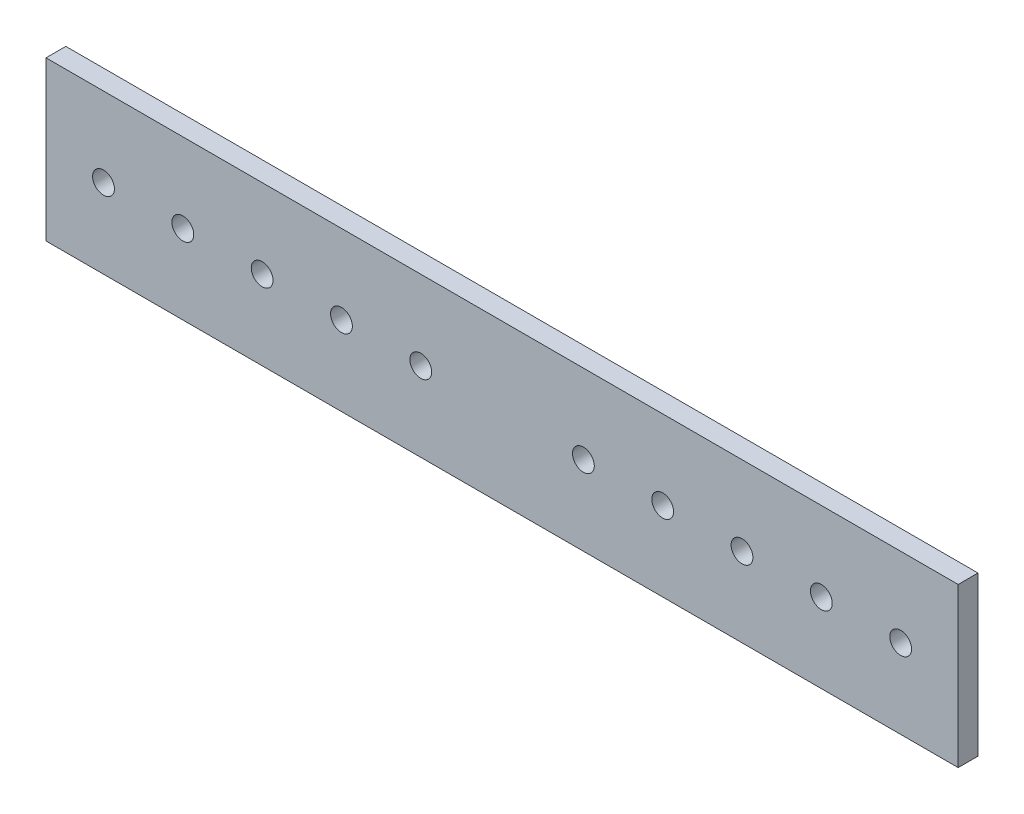
SolidWorks part; units mm, degrees
ref_plane "Plan de face" through (0, 0, 0) normal (0, 0, 1) x (1, 0, 0)
ref_plane "Plan de dessus" through (0, 0, 0) normal (0, 1, 0) x (1, 0, 0)
ref_plane "Plan de droite" through (0, 0, 0) normal (1, 0, 0) x (0, 0, -1)
sketch "Esquisse1" plane through (0, 0, 0) normal (0, 0, 1) x (1, 0, 0)
  line L1 (-115, -20) -> (115, -20)
  line L2 (-115, -20) -> (-115, 20)
  line L3 (-115, 20) -> (115, 20)
  line L4 (115, -20) -> (115, 20)
  line L5 (-115, -20) -> (115, 20) construction
  line L6 (-115, 20) -> (115, -20) construction
  point P0 (0, 0)
  dimension "D1" = 230
  dimension "D2" = 40
extrude "Boss.-Extru.1" add sketch "Esquisse1" along normal blind 5
sketch "Esquisse2" plane through (0, 0, 5) normal (0, 0, 1) x (1, 0, 0)
  circle A0 centre (0, 0) radius 20.5 construction
  circle A1 centre (20.5, 0) radius 2.75
  dimension "D1" = 41
  dimension "D2" = 5.5
extrude "Enlèv. mat.-Extru.1" cut sketch "Esquisse2" against normal through all
sketch "Esquisse8" plane through (0, 0, 0) normal (0, 0, -1) x (-1, 0, 0)
  circle A0 centre (20.5, 0) radius 2.75
  dimension "D2" = 5.5
  dimension "D1" = 20.5
extrude "Enlèv. mat.-Extru.2" cut sketch "Esquisse8" against normal blind 5
pattern_linear "Répétition linéaire2" count 5 spacing 20 along (1, 0, 0) of "Enlèv. mat.-Extru.1"
pattern_linear "Répétition linéaire3" count 5 spacing 20 along (-1, 0, 0) of "Enlèv. mat.-Extru.2"
ref_point "Point1"
ref_point "Point2"
ref_axis "Axis2" through (0, 0, 0) along (0, 0, -1)
